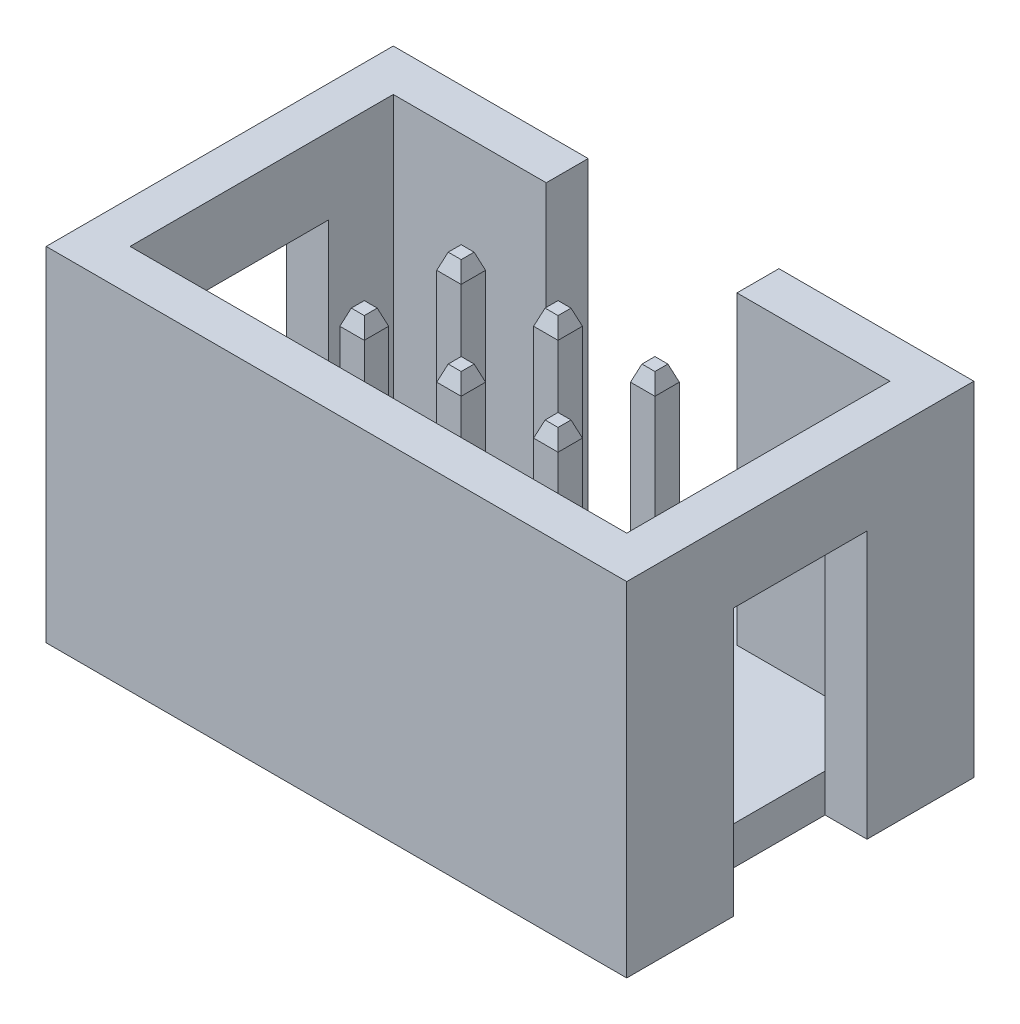
SolidWorks part; units mm, degrees
note: The reader was unsure of these and kept them because the rebuilt part matched: shared geometry of "Эскиз2<3>".
ref_plane "Спереди" through (0, 0, 0) normal (0, 0, 1) x (1, 0, 0)
ref_plane "Сверху" through (0, 0, 0) normal (0, 1, 0) x (1, 0, 0)
ref_plane "Справа" through (0, 0, 0) normal (1, 0, 0) x (0, 0, -1)
sketch "Эскиз1" plane through (0, 0, 0) normal (0, 1, 0) x (1, 0, 0)
  line L1 (-0.32, -0.32) -> (0.32, -0.32)
  line L2 (-0.32, -0.32) -> (-0.32, 0.32)
  line L3 (-0.32, 0.32) -> (0.32, 0.32)
  line L4 (0.32, -0.32) -> (0.32, 0.32)
  line L5 (-0.32, -0.32) -> (0.32, 0.32) construction
  line L6 (-0.32, 0.32) -> (0.32, -0.32) construction
  point P0 (0, 0)
  dimension "D1" = 0.64
  dimension "D2" = 0.64
extrude "Бобышка-Вытянуть1" add sketch "Эскиз1" along normal blind 8.5 and the other way blind 3 contours L1 L4 L3 L2
chamfer "Фаска1" distance 0.15 angle 70 8 edges at (0.32, -3, 0) (0, -3, -0.32) (0, -3, 0.32) (-0.32, -3, 0) (0.32, 8.5, 0) (0, 8.5, -0.32) (-0.32, 8.5, 0) (0, 8.5, 0.32)
pattern_linear "Линейный массив1" count 3 spacing 2.54 along (1, 0, 0) count 2 spacing 2.54 along (0, 0, 1) of bodies 101
sketch "Эскиз2" plane through (0, 0, 0) normal (0, 1, 0) x (1, 0, 0)
  line L0 (0, 0) -> (5.08, -2.5187) construction
  line L1 (2.22, 0.32) -> (2.86, 0.32)
  line L2 (-5.07, -5.8093) -> (10.15, -5.8093)
  line L3 (-5.07, -5.8093) -> (-5.07, 3.2907)
  line L4 (-5.07, 3.2907) -> (10.15, 3.2907)
  line L5 (10.15, -5.8093) -> (10.15, 3.2907)
  line L6 (-5.07, -5.8093) -> (10.15, 3.2907) construction
  line L7 (-5.07, 3.2907) -> (10.15, -5.8093) construction
  line L8 (-0.32, -0.32) -> (0.32, -0.32)
  line L9 (-0.32, -0.32) -> (-0.32, 0.32)
  line L10 (-0.32, 0.32) -> (0.32, 0.32)
  line L11 (0.32, -0.32) -> (0.32, 0.32)
  line L12 (-0.32, -0.32) -> (0.32, 0.32) construction
  line L13 (-0.32, 0.32) -> (0.32, -0.32) construction
  line L14 (2.86, -0.32) -> (2.86, 0.32)
  line L15 (2.22, -0.32) -> (2.22, 0.32)
  line L16 (2.22, -0.32) -> (2.86, -0.32)
  line L17 (4.76, 0.32) -> (5.4, 0.32)
  line L18 (5.4, -0.32) -> (5.4, 0.32)
  line L19 (4.76, -0.32) -> (4.76, 0.32)
  line L20 (4.76, -0.32) -> (5.4, -0.32)
  line L21 (2.22, -2.22) -> (2.86, -2.22)
  line L22 (2.86, -2.86) -> (2.86, -2.22)
  line L23 (2.22, -2.86) -> (2.22, -2.22)
  line L24 (2.22, -2.86) -> (2.86, -2.86)
  line L25 (4.76, -2.22) -> (5.4, -2.22)
  line L26 (5.4, -2.86) -> (5.4, -2.22)
  line L27 (4.76, -2.86) -> (4.76, -2.22)
  line L28 (4.76, -2.86) -> (5.4, -2.86)
  line L29 (-0.32, -2.22) -> (0.32, -2.22)
  line L30 (0.32, -2.86) -> (0.32, -2.22)
  line L31 (-0.32, -2.86) -> (-0.32, -2.22)
  line L32 (-0.32, -2.86) -> (0.32, -2.86)
  line L33 (2.54, -1.2593) -> (2.54, 49998.7407) construction
  line L34 (9.05, -4.7093) -> (-3.97, -4.7093)
  line L35 (9.05, -4.7093) -> (9.05, 2.1907)
  line L36 (9.05, 2.1907) -> (-3.97, 2.1907)
  line L37 (-3.97, -4.7093) -> (-3.97, 2.1907)
  line L38 (9.05, -4.7093) -> (-3.97, 2.1907) construction
  line L39 (9.05, 2.1907) -> (-3.97, -4.7093) construction
  line L40 (0.04, 3.2907) -> (0.04, 2.1907)
  line L41 (5.04, 3.2907) -> (5.04, 2.1907)
  point P3 (2.54, -1.2593)
  point P13 (2.54, -1.2593)
  dimension "D3" = 15.22
  dimension "D4" = 9.1
  dimension "D5" = 1.1
  dimension "D6" = 1.1
  dimension "D7" = 5
  dimension "D1" = 3
  dimension "D2" = 2
extrude "Бобышка-Вытянуть2" add sketch "Эскиз2" along normal blind 1 contours L37 L34 L35 L36 L32 L31 L29 L30 L28 L27 L25 L26 L24 L23 L21 L22 L20 L19 L17 L18 L16 L15 L1 L14 L11 L8 L9 L10 | L41 L4 L40 L36
extrude "Бобышка-Вытянуть3" add sketch "Эскиз2<3>" along normal blind 9 contours L4 L41 L36 L35 L34 L37 L40 L3 L2 L5
sketch "Эскиз2<3>" plane through (0, 0, 0) normal (0, 1, 0) x (1, 0, 0) same geometry as "Эскиз2"
sketch "Эскиз3" plane through (0, 0, 0) normal (0, -1, 0) x (1, 0, 0)
  line L0 (-3.97, 1.2593) -> (-5.07, 1.2593) construction
  line L1 (-3.97, 4.7093) -> (-3.97, -2.1907) construction
  line L2 (-5.07, 5.8093) -> (-5.07, -3.2907) construction
  line L3 (9.05, 1.2593) -> (10.15, 1.2593) construction
  line L4 (9.05, 4.7093) -> (9.05, -2.1907) construction
  line L5 (10.15, 5.8093) -> (10.15, -3.2907) construction
  line L7 (-5.07, -0.4907) -> (-3.97, -0.4907)
  line L8 (-5.07, -0.4907) -> (-5.07, 3.0093)
  line L9 (-5.07, 3.0093) -> (-3.97, 3.0093)
  line L10 (-3.97, -0.4907) -> (-3.97, 3.0093)
  line L11 (-5.07, -0.4907) -> (-3.97, 3.0093) construction
  line L12 (-5.07, 3.0093) -> (-3.97, -0.4907) construction
  line L13 (9.05, -0.4907) -> (10.15, -0.4907)
  line L14 (9.05, -0.4907) -> (9.05, 3.0093)
  line L15 (9.05, 3.0093) -> (10.15, 3.0093)
  line L16 (10.15, -0.4907) -> (10.15, 3.0093)
  line L17 (9.05, -0.4907) -> (10.15, 3.0093) construction
  line L18 (9.05, 3.0093) -> (10.15, -0.4907) construction
  point P12 (-4.52, 1.2593)
  point P17 (9.6, 1.2593)
  line M8 (-5.07, 5.8093) -> (-5.07, -3.2907)
  dimension "D1" = 3.5
  dimension "D2" = 3.5
extrude "Вырез-Вытянуть2" cut sketch "Эскиз3" against normal blind 7 contours L7 L10 L9 M8 | L15 L16 L13 L14
